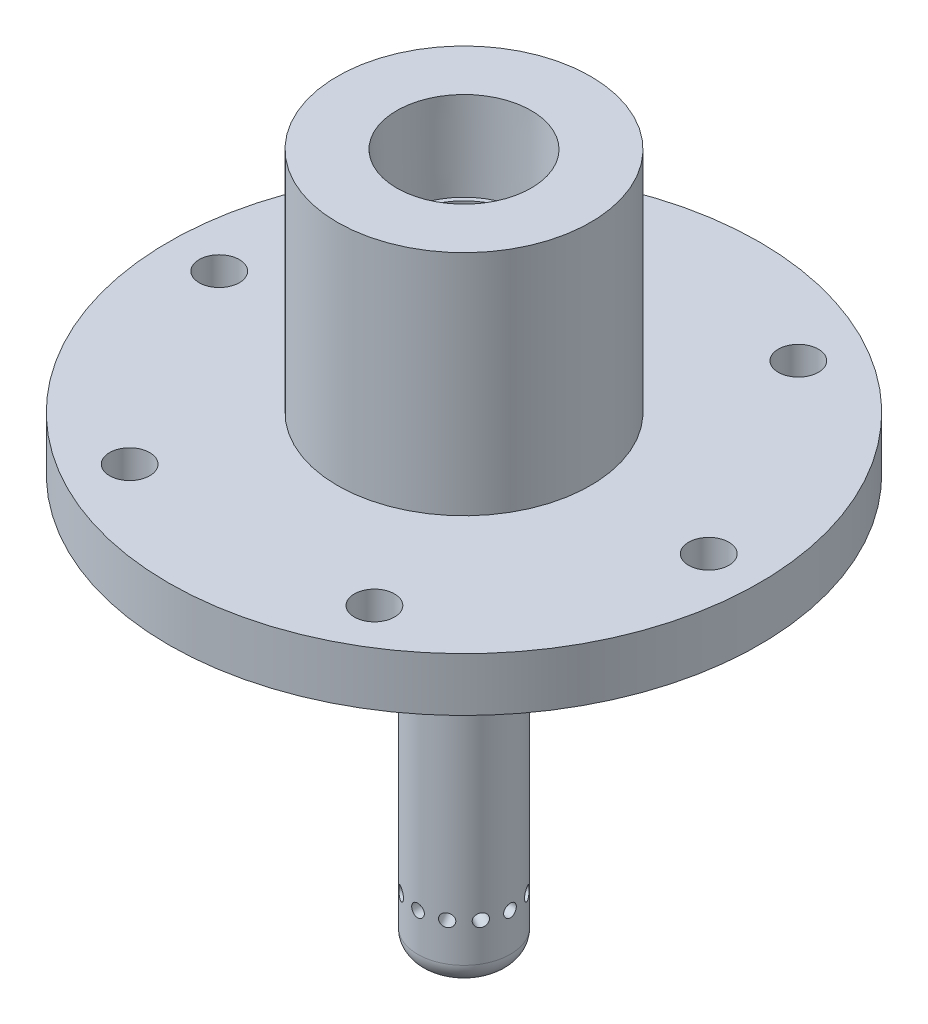
SolidWorks part; units mm, degrees
ref_plane "Front Plane" through (0, 0, 0) normal (0, 0, 1) x (1, 0, 0)
ref_plane "Top Plane" through (0, 0, 0) normal (0, 1, 0) x (1, 0, 0)
ref_plane "Right Plane" through (0, 0, 0) normal (1, 0, 0) x (0, 0, -1)
sketch "Sketch1" plane through (0, 0, 0) normal (0, 0, 1) x (1, 0, 0)
  line L0 (0, 0) -> (-15, 0)
  line L1 (-15, 0) -> (-15, -27)
  line L2 (-15, -27) -> (-35, -27)
  line L3 (-35, -27) -> (-35, -33.35)
  line L4 (-35, -33.35) -> (-16, -33.35)
  line L5 (-10, -35.85) -> (-10, -40.85)
  line L6 (-10, -40.85) -> (-5.5, -45.35)
  line L7 (-5.5, -45.35) -> (-5.5, -79.85)
  line L8 (-3, -82.35) -> (0, -82.35)
  line L9 (0, -82.35) -> (0, 0)
  line L11 (-10, -35.85) -> (-16, -35.85)
  line L12 (-16, -35.85) -> (-16, -33.35)
  line L13 (-10, -35.85) -> (0, -35.85) construction
  arc A0 (-5.5, -79.85) -> (-3, -82.35) centre (-3, -79.85) ccw
  point P7 (-10, -33.35)
  point P15 (-5.5, -82.35)
  dimension "D9" = 2.5
  dimension "D1" = 5.5
  dimension "D2" = 10
  dimension "D3" = 37
  dimension "D4" = 45
  dimension "D5" = 6.35
  dimension "D6" = 5
  dimension "D7" = 15
  dimension "D8" = 25
  dimension "D11" = 2.5
  dimension "D10" = 27
  dimension "D12" = 16
revolve "Revolve1" add sketch "Sketch1" angle 360 about L9
hole_wizard "Ø6.0 (6) Diameter Hole1" positions "Sketch2" profile "Sketch4" hole size "Ø6.0" standard "ISO"
sketch "Sketch2" plane through (0, 0, 0) normal (0, 1, 0) x (1, 0, 0)
  point P0 (0, 0)
sketch "Sketch4" plane through (0, 0, 0) normal (1, 0, 0) x (0, 0, 1)
  line L0 (0, 0) -> (0, 80)
  line L1 (0, 80) -> (3, 78.1974)
  line L2 (3, 78.1974) -> (3, 0)
  line L5 (3, 0) -> (0, 0)
  line L10 (0, 80) -> (-3, 78.1974) construction
  line L11 (0, -6.35) -> (0, 107.95) construction
  dimension "Hole Dia." = 6
  dimension "Hole Depth" = 80
  dimension "Drill Angle" = 118
sketch "Sketch5" plane through (0, -33.35, 0) normal (0, -1, 0) x (-1, 0, 0)
  circle A0 centre (0, 0) radius 21
  circle A1 centre (0, 0) radius 24
  dimension "D1" = 42
  dimension "D2" = 48
extrude "Cut-Extrude1" cut sketch "Sketch5" against normal blind 3
hole_wizard "3/16 (0.1875) Diameter Hole1" positions "Sketch6" profile "Sketch8" hole size "3/16" standard "ANSI Inch" end condition through all
sketch "Sketch6" plane through (0, -27, 0) normal (0, 1, 0) x (1, 0, 0)
  point P0 (29, 0)
  dimension "D1" = 29
sketch "Sketch8" plane through (29, -27, 0) normal (1, 0, 0) x (0, 0, 1)
  line L0 (0, 0) -> (0, 55.35)
  line L1 (0, 55.35) -> (2.3812, 55.35)
  line L2 (2.3812, 55.35) -> (2.3812, 0)
  line L5 (2.3812, 0) -> (0, 0)
  line L11 (0, -6.35) -> (0, 107.95) construction
  dimension "Thru Hole Dia." = 4.7625
  dimension "Thru Hole Depth" = 55.35
pattern_circular "CirPattern1" count 6 over 360 about axis through (0, -82.35, 0) along (0, -1, 0) of "3/16 (0.1875) Diameter Hole1" reverse direction yes
ref_plane "Plane1" through (0, 0, 10) normal (0, 0, 1) x (1, 0, 0)
sketch "Sketch9" plane through (0, 0, 10) normal (0, 0, 1) x (1, 0, 0)
  line L0 (0, -76.1) -> (0, -74.6) construction
  line L2 (0, -74.6) -> (0, -75.35) construction
  line L3 (0, -75.35) -> (0, 0) construction
  circle A0 centre (0, -75.35) radius 0.75
  dimension "D1" = 39.5
  dimension "Outlet Diameter" = 1.5
extrude "Cut-Extrude2" cut sketch "Sketch9" against normal blind 10
pattern_circular "CirPattern2" count 12 over 360 about axis through (0, -79.85, 0) along (0, -1, 0) of "Cut-Extrude2"
hole_wizard "3/8 NPT Tapped Hole1" positions "Sketch10" profile "Sketch11" size "3/8" standard "ANSI Inch"
sketch "Sketch10" plane through (0, 0, 0) normal (0, 1, 0) x (1, 0, 0)
  point P0 (0, 0)
sketch "Sketch11" plane through (0, 0, 0) normal (1, 0, 0) x (0, 0, 1)
  line L0 (0, 0) -> (0, 17.38)
  line L1 (7.1374, 13.0914) -> (0, 17.38)
  line L2 (-7.1374, 13.0914) -> (0, 17.38) construction
  line L3 (7.1374, 13.0914) -> (7.1374, 10.33)
  line L4 (7.1374, 10.33) -> (7.6537, 10.33)
  line L5 (7.6537, 10.33) -> (7.963, 0)
  line L6 (-7.6537, 10.33) -> (-7.963, 0) construction
  line L7 (7.963, 0) -> (0, 0)
  line L8 (0, -6.35) -> (0, 107.95) construction
  line L11 (-7.1374, 10.33) -> (-7.6537, 10.33) construction
  dimension "Tap Drill Dia." = 14.2748
  dimension "Tap Drill Depth" = 17.38
  dimension "Thread Dia." = 15.9261
  dimension "Thread Angle" = 3.43
  dimension "Thread Depth" = 10.33
  dimension "Drill Angle" = 118
cosmetic thread "Hole Thread1" parameters "D1"=10.33, "D2"=17.145
surface "Surface-Fill1" [suppressed]
thicken "Thicken1" [suppressed] surfaces to thicken 109 thickness 0.254 parameters "D1"=0.254
surface "Surface-Fill2" [suppressed]
thicken "Thicken2" [suppressed] surfaces to thicken 111 thickness 0.254 parameters "D1"=0.254
pattern_circular "CirPattern3" [suppressed] count 8 over 360 of bodies 112
